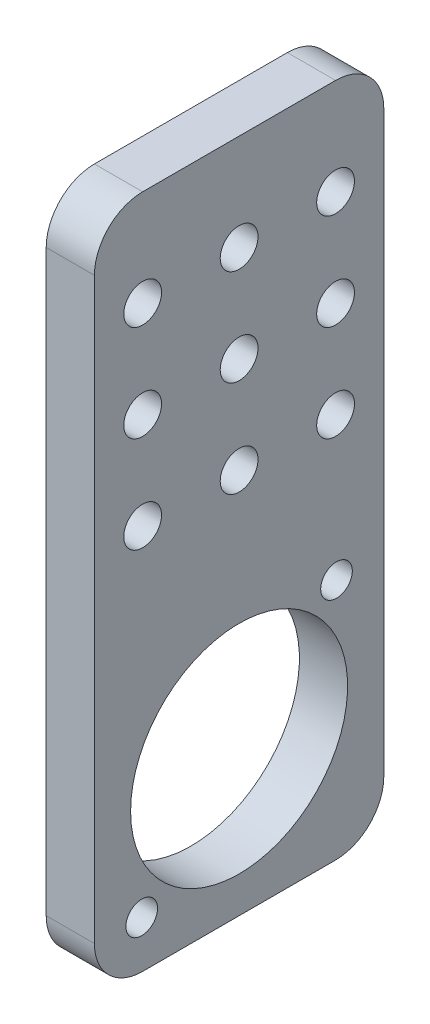
SolidWorks part; units mm, degrees
material "1060 Alloy"
ref_plane "Front Plane" through (0, 0, 0) normal (0, 0, 1) x (1, 0, 0)
ref_plane "Top Plane" through (0, 0, 0) normal (0, 1, 0) x (1, 0, 0)
ref_plane "Right Plane" through (0, 0, 0) normal (1, 0, 0) x (0, 0, -1)
ref_plane "Plane1" through (95.25, 0, 0) normal (1, 0, 0) x (0, 0, -1)
sketch "Sketch1" plane through (95.25, 0, 0) normal (1, 0, 0) x (0, 0, -1)
  line L0 (-184.15, -107.95) -> (-184.15, -31.75)
  line L1 (-190.5, -25.4) -> (-215.9, -25.4)
  line L2 (-222.25, -31.75) -> (-222.25, -107.95)
  line L3 (-215.9, -114.3) -> (-190.5, -114.3)
  circle A0 centre (-190.3762, -82.4262) radius 2.0828
  circle A1 centre (-216.0238, -108.0738) radius 2.0828
  circle A2 centre (-203.2, -95.25) radius 14.2875
  arc A3 (-184.15, -31.75) -> (-190.5, -25.4) centre (-190.5, -31.75) ccw
  arc A4 (-215.9, -25.4) -> (-222.25, -31.75) centre (-215.9, -31.75) ccw
  arc A5 (-222.25, -107.95) -> (-215.9, -114.3) centre (-215.9, -107.95) ccw
  arc A6 (-190.5, -114.3) -> (-184.15, -107.95) centre (-190.5, -107.95) ccw
  circle A7 centre (-215.9, -38.1) radius 2.4892
  circle A8 centre (-203.2, -38.1) radius 2.4892
  circle A9 centre (-190.5, -38.1) radius 2.4892
  circle A10 centre (-215.9, -63.5) radius 2.4892
  circle A11 centre (-203.2, -63.5) radius 2.4892
  circle A12 centre (-190.5, -63.5) radius 2.4892
  circle A13 centre (-215.9, -50.8) radius 2.4892
  circle A14 centre (-203.2, -50.8) radius 2.4892
  circle A15 centre (-190.5, -50.8) radius 2.4892
extrude "Boss-Extrude1" add sketch "Sketch1" against normal blind 6.35
